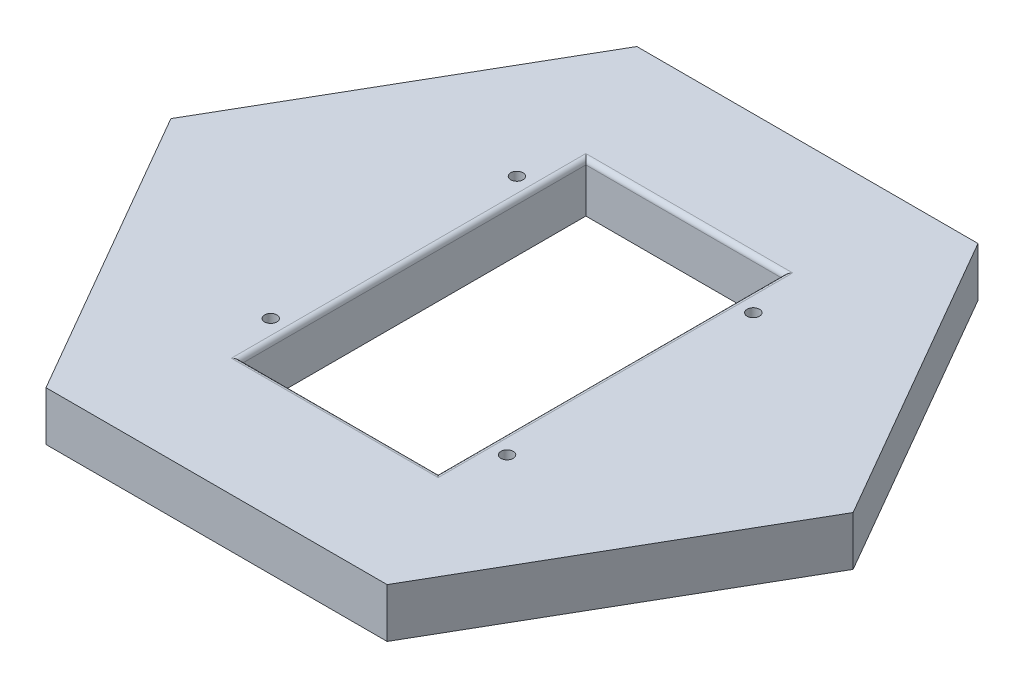
SolidWorks part; units mm, degrees
ref_plane "Front Plane" through (0, 0, 0) normal (0, 0, 1) x (1, 0, 0)
ref_plane "Top Plane" through (0, 0, 0) normal (0, 1, 0) x (1, 0, 0)
ref_plane "Right Plane" through (0, 0, 0) normal (1, 0, 0) x (0, 0, -1)
sketch "Sketch1" plane through (0, 0, 0) normal (0, 1, 0) x (1, 0, 0)
  line L1 (69.282, 0) -> (34.641, 60)
  line L2 (34.641, 60) -> (-34.641, 60)
  line L3 (-34.641, 60) -> (-69.282, 0)
  line L4 (-69.282, 0) -> (-34.641, -60)
  line L5 (-34.641, -60) -> (34.641, -60)
  line L6 (34.641, -60) -> (69.282, 0)
  circle A0 centre (0, 0) radius 60 construction
  dimension "D1" = 120
extrude "Boss-Extrude1" add sketch "Sketch1" along normal mid plane 10
sketch "Sketch2" plane through (0, -5, 0) normal (0, -1, 0) x (-1, 0, 0)
  line L0 (0, 0) -> (-34.641, -60) construction
  line L1 (34.641, -60) -> (-34.641, -60) construction
  line L2 (-34.641, -60) -> (-69.282, 0) construction
  line L3 (-69.282, 0) -> (-34.641, 60) construction
  circle A0 centre (-25.9808, -45) radius 9
  circle A1 centre (-51.9615, 0) radius 9
  circle A2 centre (-25.9808, 45) radius 9
  circle A3 centre (25.9808, 45) radius 9
  circle A4 centre (51.9615, 0) radius 9
  circle A5 centre (25.9808, -45) radius 9
  point P20 (0, 0)
  dimension "D1" = 18
  dimension "D2" = 15
  dimension "D3" = 6
  dimension "D4" = 15
  dimension "D5" = 15
extrude "Cut-Extrude1" cut sketch "Sketch2" against normal blind 5
sketch "Sketch3" plane through (0, 5, 0) normal (0, 1, 0) x (1, 0, 0)
  line L0 (0, 0) -> (21.3132, 0) construction
  line L6 (-20, 35) -> (20, 35)
  line L7 (-20, 35) -> (-20, -35)
  line L8 (-20, -35) -> (20, -35)
  line L9 (20, 35) -> (20, -35)
  line L10 (-20, 35) -> (20, -35) construction
  line L11 (-20, -35) -> (20, 35) construction
  circle A2 centre (-24, 25) radius 1.25
  circle A3 centre (24, 25) radius 1.25
  circle A4 centre (24, -25) radius 1.25
  circle A5 centre (-24, -25) radius 1.25
  point P1 (0, 0)
  point P16 (0, 0)
  point P17 (0, 0)
  point P18 (0, 0)
  dimension "D1" = 70
  dimension "D3" = 2.5
  dimension "D7" = 25
  dimension "D5" = 25
  dimension "D2" = 40
  dimension "D4" = 24
  dimension "D6" = 24
extrude "Cut-Extrude2" cut sketch "Sketch3" against normal blind 10
fillet "Fillet1" radius 1 4 edges at (0, 5, 35) (20, 5, 0) (0, 5, -35) (-20, 5, 0)
